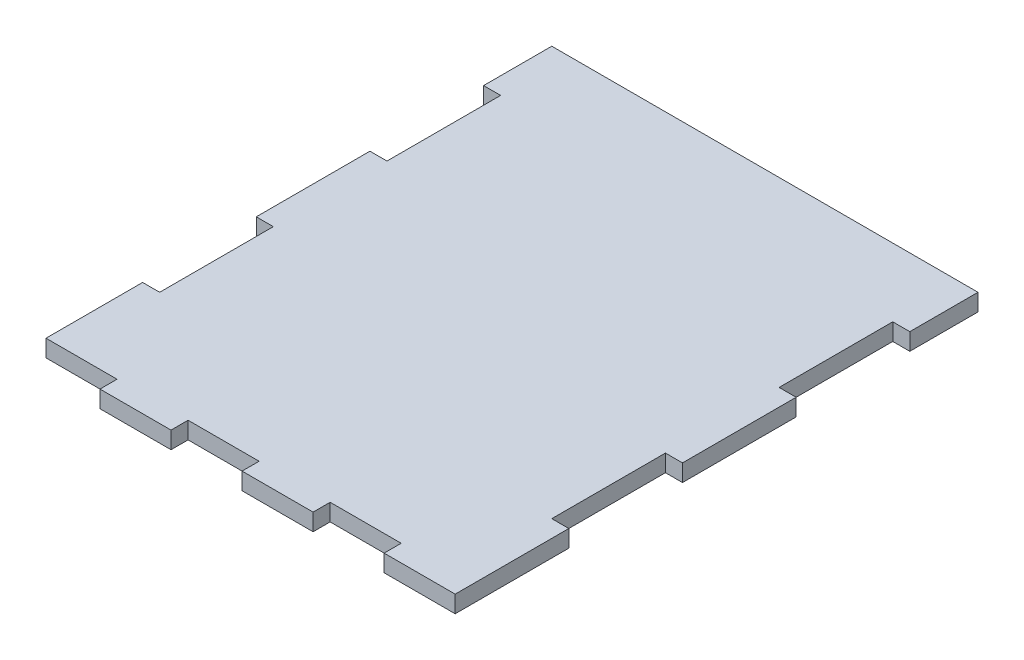
SolidWorks part; units mm, degrees
material "Pine"
ref_plane "Front Plane" through (0, 0, 0) normal (0, 0, 1) x (1, 0, 0)
ref_plane "Top Plane" through (0, 0, 0) normal (0, 1, 0) x (1, 0, 0)
ref_plane "Right Plane" through (0, 0, 0) normal (1, 0, 0) x (0, 0, -1)
sketch "Sketch1" plane through (0, 0, 0) normal (0, 1, 0) x (1, 0, 0)
  line L1 (-75, 92) -> (75, 92)
  line L2 (-75, 92) -> (-75, -92)
  line L3 (-75, -92) -> (75, -92)
  line L4 (75, 92) -> (75, -92)
  line L5 (-75, 92) -> (75, -92) construction
  line L6 (-75, -92) -> (75, 92) construction
  point P0 (0, 0)
  dimension "D1" = 150
  dimension "D2" = 184
extrude "Boss-Extrude1" add sketch "Sketch1" along normal blind 6
sketch "Sketch2" plane through (0, 6, 0) normal (0, 1, 0) x (1, 0, 0)
  line L0 (-75, 92) -> (-75, -92) construction
  line L1 (-75, 68) -> (-69, 68)
  line L2 (-75, 68) -> (-75, 28)
  line L3 (-75, 28) -> (-69, 28)
  line L4 (-69, 68) -> (-69, 28)
  line L5 (75, 92) -> (-75, 92) construction
  line L6 (69, 68) -> (69, 28)
  line L7 (69, 68) -> (75, 68)
  line L8 (75, 68) -> (75, 28)
  line L9 (69, 28) -> (75, 28)
  line L10 (69, -12) -> (69, -52)
  line L11 (69, -12) -> (75, -12)
  line L12 (75, -12) -> (75, -52)
  line L13 (69, -52) -> (75, -52)
  line L14 (-75, -12) -> (-75, -52)
  line L15 (-75, -12) -> (-69, -12)
  line L16 (-69, -12) -> (-69, -52)
  line L17 (-75, -52) -> (-69, -52)
  dimension "D1" = 24
  dimension "D2" = 40
  dimension "D3" = 6
  dimension "D4" = 2
  dimension "D5" = 2
extrude "Cut-Extrude1" cut sketch "Sketch2" against normal blind 6
sketch "Sketch6" plane through (0, 6, 0) normal (0, 1, 0) x (1, 0, 0)
  line L1 (75, -92) -> (75, -52) construction
  circle A0 centre (16, 10) radius 1.23
  dimension "D1" = 2.46
  dimension "D2" = 102
  dimension "D3" = 59
extrude "Cut-Extrude6" [suppressed] cut sketch "Sketch6" against normal through all
sketch "Sketch7" plane through (0, 6, 0) normal (0, 1, 0) x (1, 0, 0)
  line L0 (75, -92) -> (75, -52) construction
  line L1 (-75, -92) -> (75, -92) construction
  circle A0 centre (16, 55) radius 2
  dimension "D1" = 59
  dimension "D2" = 147
extrude "Cut-Extrude7" [suppressed] cut sketch "Sketch7" against normal through all
sketch "Sketch8" plane through (0, 6, 0) normal (0, 1, 0) x (1, 0, 0)
  line L0 (75, 68) -> (75, 92) construction
  line L1 (-75, -92) -> (75, -92) construction
  circle A0 centre (-16, 55) radius 2.38
  dimension "D1" = 91
  dimension "D2" = 147
extrude "Cut-Extrude8" [suppressed] cut sketch "Sketch8" against normal through all
sketch "Sketch9" plane through (0, 6, 0) normal (0, 1, 0) x (1, 0, 0)
  circle A0 centre (30.25, -1) radius 2.55
  circle A1 centre (30.25, -11) radius 2.55
  circle A2 centre (-19.25, -1) radius 2.55
  circle A3 centre (-19.25, -11) radius 2.55
  dimension "D1" = 49.5
  dimension "D2" = 0
  dimension "D3" = 10
  dimension "D4" = 0
  dimension "D5" = 49.5
  dimension "D6" = 0
  dimension "D7" = 93
  dimension "D8" = 55.75
extrude "Cut-Extrude9" [suppressed] cut sketch "Sketch9" against normal through all
sketch "Sketch11" plane through (0, 6, 0) normal (0, 1, 0) x (1, 0, 0)
  line L0 (-25, -92) -> (-25, -86)
  line L1 (-75, -92) -> (-50, -92)
  line L2 (-75, -92) -> (-75, -86)
  line L3 (-75, -86) -> (-50, -86)
  line L4 (-50, -92) -> (-50, -86)
  line L5 (-25, -92) -> (0, -92)
  line L6 (0, -92) -> (0, -86)
  line L7 (-25, -86) -> (0, -86)
  line L8 (25, -92) -> (25, -86)
  line L9 (25, -92) -> (50, -92)
  line L10 (50, -92) -> (50, -86)
  line L11 (25, -86) -> (50, -86)
  dimension "D1" = 6
  dimension "D2" = 25
  dimension "D3" = 3
extrude "Cut-Extrude10" cut sketch "Sketch11" against normal blind 6
